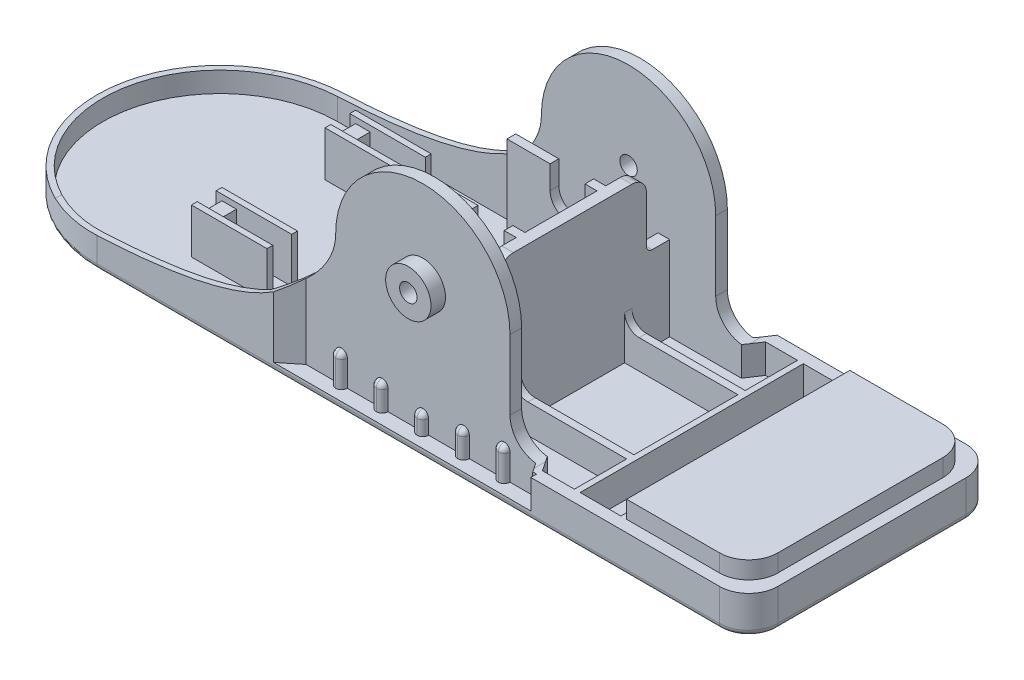
SolidWorks part; units mm, degrees
ref_plane "Front Plane" through (0, 0, 0) normal (0, 0, 1) x (1, 0, 0)
ref_plane "Top Plane" through (0, 0, 0) normal (0, 1, 0) x (1, 0, 0)
ref_plane "Right Plane" through (0, 0, 0) normal (1, 0, 0) x (0, 0, -1)
sketch "Sketch1" plane through (0, 0, 0) normal (0, 1, 0) x (1, 0, 0)
  line L0 (-66.675, 0) -> (-45.475, 0)
  line L1 (-45.475, -21.2) -> (66.675, -21.2)
  line L2 (-66.675, -21.2) -> (-66.675, 0) construction
  line L3 (-45.475, 21.2) -> (66.675, 21.2)
  line L4 (66.675, -21.2) -> (66.675, 21.2)
  line L5 (-66.675, -21.2) -> (66.675, 21.2) construction
  line L6 (-66.675, 21.2) -> (66.675, -21.2) construction
  line L7 (-66.675, 0) -> (-66.675, 21.2) construction
  line L8 (-66.675, 21.2) -> (-45.475, 21.2) construction
  line L9 (-66.675, -21.2) -> (-45.475, -21.2) construction
  arc A0 (-45.475, 21.2) -> (-45.475, -21.2) centre (-45.475, 0) ccw
  arc A1 (-45.475, -21.2) -> (-25.946, -8.2498) centre (-45.475, 0) ccw construction
  arc A2 (-25.946, -8.2498) -> (-25.946, 8.2498) centre (-45.475, 0) ccw construction
  arc A3 (-25.946, 8.2498) -> (-45.475, 21.2) centre (-45.475, 0) ccw construction
  point P0 (0, 0)
  dimension "D1" = 133.35
  dimension "D2" = 42.4
  dimension "D3" = 21.2
extrude "Boss-Extrude1" add sketch "Sketch1" along normal blind 1.5 contours L3 L4 L1 A0
fillet "Fillet1" radius 5 2 edges at (66.675, 0.75, -21.2) (66.675, 0.75, 21.2)
sketch "Sketch3" plane through (0, 1.5, 0) normal (0, 1, 0) x (1, 0, 0)
  line L0 (66.675, -21.2) -> (29.175, -21.2)
  line L1 (-45.475, -21.2) -> (61.675, -21.2) construction
  line L2 (29.175, -21.2) -> (29.175, 21.2)
  line L3 (-45.475, 21.2) -> (61.675, 21.2) construction
  line L4 (29.175, 21.2) -> (66.675, 21.2)
  line L5 (66.675, 21.2) -> (66.675, -21.2)
  line L6 (59.675, -19.2) -> (31.175, -19.2)
  line L8 (31.175, 19.2) -> (59.675, 19.2)
  line L9 (64.675, 14.2) -> (64.675, -14.2)
  line L10 (31.175, 19.2) -> (64.675, 19.2) construction
  line L11 (64.675, 19.2) -> (64.675, -19.2) construction
  line L12 (64.675, -19.2) -> (31.175, -19.2) construction
  line L13 (64.675, -19.2) -> (35.675, -19.2)
  line L14 (31.175, -19.2) -> (29.175, -19.2)
  line L15 (35.675, -19.2) -> (34.675, -19.2)
  line L16 (35.675, -19.2) -> (35.675, 19.2)
  line L17 (35.675, 19.2) -> (34.675, 19.2)
  line L18 (34.675, -19.2) -> (34.675, 19.2)
  line L19 (31.175, 19.2) -> (29.175, 19.2)
  line L20 (64.675, -0.7956) -> (43.675, -0.7956) construction
  line L21 (31.175, -19.2) -> (31.175, 19.2) construction
  line L23 (43.675, 19.2) -> (42.675, 19.2)
  line L24 (43.675, 19.2) -> (43.675, -19.2)
  line L25 (43.675, -19.2) -> (42.675, -19.2)
  line L26 (42.675, 19.2) -> (42.675, -19.2)
  arc A0 (59.675, 19.2) -> (64.675, 14.2) centre (59.675, 14.2) cw
  arc A1 (59.675, -19.2) -> (64.675, -14.2) centre (59.675, -14.2) ccw
  line M21 (66.675, -16.2) -> (66.675, 16.2)
  arc M22 (66.675, 16.2) -> (61.675, 21.2) centre (61.675, 16.2) ccw
  line M23 (61.675, 21.2) -> (-45.475, 21.2)
  line M25 (-45.475, -21.2) -> (61.675, -21.2)
  arc M26 (61.675, -21.2) -> (66.675, -16.2) centre (61.675, -16.2) ccw
  dimension "D3" = 5
  dimension "D1" = 37.5
  dimension "D4" = 29
  dimension "D5" = 1
  dimension "D6" = 0
  dimension "D7" = 21
  dimension "D8" = 1
  dimension "D2" = 2
extrude "Boss-Extrude2" add sketch "Sketch3" along normal blind 5 contours A1 L6 L13 L14 L2 L19 L8 A0 L9 M25 M26 M21 M22 M23 | L26 L25 L24 L23 | L16 L17 L18 L15 region at (45.425, 1.5, 20.634)
extrude "Boss-Extrude3" add sketch "Sketch3<3>" along normal blind 8 separate body contours L6 A1 L9 A0 L8 L24 region at (54.0485, 1.5, 0)
sketch "Sketch3<3>" plane through (0, 1.5, 0) normal (0, 1, 0) x (1, 0, 0) same geometry as "Sketch3"
sketch "Sketch6" plane through (0, 1.5, 0) normal (0, 1, 0) x (1, 0, 0)
  line L0 (29.175, -21.2) -> (27.5167, -18.7)
  line L1 (29.175, -21.2) -> (61.675, -21.2) construction
  line L2 (29.175, -19.2) -> (27.5167, -16.7)
  line L3 (-45.475, -21.2) -> (29.175, -21.2) construction
  line L4 (27.5167, -18.7) -> (-11.9833, -18.7)
  line L5 (27.5167, -16.7) -> (-11.9833, -16.7)
  line L6 (-11.9833, -18.7) -> (-15.1058, -21.2)
  line L7 (-11.9833, -16.7) -> (-16.3548, -20.2)
  line L8 (-45.475, 21.2) -> (29.175, 21.2) construction
  line L9 (-45.475, 21.2) -> (-16.3548, 21.2)
  line L10 (28.5117, -20.2) -> (29.175, -20.2)
  line L11 (-45.475, -20.2) -> (29.175, -20.2)
  line L12 (-45.475, -20.2) -> (-16.3548, -20.2)
  line L13 (-16.3548, -20.2) -> (-13.8568, -20.2) construction
  line L14 (-13.8568, -20.2) -> (28.5117, -20.2) construction
  line L15 (-45.475, -21.2) -> (-16.3548, -21.2)
  line L16 (27.5167, 16.7) -> (-11.9833, 16.7)
  line L17 (-16.3548, 21.2) -> (-15.1058, 21.2)
  line L18 (-16.3548, -21.2) -> (-15.1058, -21.2)
  line L19 (29.175, -19.2) -> (29.175, -21.2)
  line L20 (-45.475, 20.2) -> (-16.3548, 20.2)
  line L21 (-11.9833, 16.7) -> (-16.3548, 20.2)
  line L22 (-11.9833, 18.7) -> (-15.1058, 21.2)
  line L23 (27.5167, 18.7) -> (-11.9833, 18.7)
  line L24 (29.175, 19.2) -> (27.5167, 16.7)
  line L25 (29.175, 21.2) -> (27.5167, 18.7)
  line L26 (29.175, 19.2) -> (29.175, 21.2)
  arc A0 (-45.475, 21.2) -> (-45.475, -21.2) centre (-45.475, 0) ccw
  arc A4 (-45.475, 20.2) -> (-45.475, -20.2) centre (-45.475, 0) ccw
  arc A5 (-45.475, 20.2) -> (-45.475, -20.2) centre (-45.475, 0) ccw
  line M22 (29.175, 19.2) -> (29.175, 21.2)
  line M23 (29.175, 21.2) -> (-45.475, 21.2)
  arc M24 (-45.475, 21.2) -> (-45.475, -21.2) centre (-45.475, 0) ccw
  line M25 (-45.475, -21.2) -> (29.175, -21.2)
  line M26 (29.175, -21.2) -> (29.175, -19.2)
  dimension "D1" = 2.5
  dimension "D2" = 3
  dimension "D3" = 39.5
  dimension "D4" = 2.5
  dimension "D5" = 2
  dimension "D6" = 4
  dimension "D7" = 2.5
  dimension "D9" = 3
  dimension "D10" = 2.5
  dimension "D8" = 1
  dimension "D11" = 1
extrude "Boss-Extrude4" add sketch "Sketch6" along normal blind 37 contours A5 L20 L21 L16 L24 L25 L23 L22 L6 L4 L0 L10 L2 L5 L7 L12 M22 M23 M24 M25 M26 region at (6.9463, 1.5, 17.8201) region at (-15.7303, 1.5, 21.0952)
sketch "Sketch9" plane through (0, 0, 21.2) normal (0, 0, 1) x (1, 0, 0)
  line L0 (-66.675, 38.5) -> (-45.475, 38.5)
  line L1 (8.1, 0) -> (8.1, 23.5)
  line L2 (-45.475, 0) -> (61.675, 0) construction
  line L3 (8.1, 0) -> (-141.45, 0)
  line L4 (-66.675, 0) -> (-66.675, 5)
  line L5 (-66.675, 5) -> (-13.2209, 5) construction
  line L6 (-66.675, 5) -> (-66.675, 38.5)
  line L7 (8.1, 38.5) -> (-66.675, 38.5)
  line L8 (29.175, 6.5) -> (23.1, 23.5)
  line L9 (23.1, 23.5) -> (23.1, 11.5)
  line L10 (28.1, 6.5) -> (29.175, 6.5)
  line L11 (8.1, 38.5) -> (29.175, 38.5)
  line L12 (29.175, 38.5) -> (29.175, 6.5)
  circle A0 centre (8.1, 23.5) radius 15
  arc A1 (23.1, 11.5) -> (28.1, 6.5) centre (28.1, 11.5) ccw
  spline S0 degree 3 poles (-6.9, 23.5) (-6.9, 19.2277) (-18.2844, 4.0271) (-52.7634, 5) (-66.675, 5) knots 0 0 0 0 0.343246 1 1 1 1
  line M10 (-15.1058, 1.5) -> (-15.1058, 38.5)
  line M11 (-15.1058, 38.5) -> (-45.475, 38.5)
  line M12 (-45.475, 38.5) -> (-45.475, 0)
  dimension "D2" = 30
  dimension "D4" = 5
  dimension "D1" = 23.5
  dimension "D3" = 5
extrude "Cut-Extrude1" cut sketch "Sketch9" against normal through all both and the other way through all contours S0 A0 L7 M10 | S0 M10 M11 M12 | L6 L5 S0 L0 M12 | A0 L8 L12 L11 | L9 A1 L10 L8 region at (-56.0848, 21.7705, 21.2) region at (-30.7898, 22.8769, 21.2) region at (-9.692, 28.6572, 21.2) region at (24.7967, 28.49, 21.2) region at (25.2303, 12.6942, 21.2)
sketch "Sketch10" plane through (0, 0, 0) normal (0, -1, 0) x (1, 0, 0)
  line L0 (-66.675, 0) -> (-56.675, 0) construction
  line L1 (-56.675, 0) -> (-45.475, 0) construction
  line L2 (-45.475, -11.2) -> (-45.475, 11.2)
  arc A0 (-45.475, 21.2) -> (-45.475, -21.2) centre (-45.475, 0) ccw construction
  arc A1 (-45.475, 11.2) -> (-45.475, -11.2) centre (-45.475, 0) ccw
  arc A2 (-45.475, -11.2) -> (-45.475, 11.2) centre (-45.475, 0) ccw construction
  point P11 (-45.475, 0)
  dimension "D1" = 22.4
extrude "Cut-Extrude2" cut sketch "Sketch10" against normal blind 0.5 contours L2 A1
sketch "Sketch11" plane through (0, 1.5, 0) normal (0, 1, 0) x (1, 0, 0)
  line L0 (29.175, 19.2) -> (29.175, 10.2) construction
  line L1 (34.675, 10.2) -> (15.175, 10.2)
  line L2 (34.675, -19.2) -> (34.675, 19.2) construction
  line L3 (29.175, -19.2) -> (29.175, -10.2) construction
  line L4 (34.675, -10.2) -> (15.175, -10.2)
  line L5 (15.175, -16.7) -> (15.175, 16.7)
  line L6 (27.5167, -16.7) -> (-11.9833, -16.7) construction
  line L7 (27.5167, 16.7) -> (-11.9833, 16.7) construction
  line L8 (23.1, -16.7) -> (-6.9, -16.7) construction
  line L9 (15.175, 16.7) -> (13.175, 16.7)
  line L10 (15.175, 16.7) -> (15.175, -16.7)
  line L11 (15.175, -16.7) -> (13.175, -16.7)
  line L12 (13.175, 16.7) -> (13.175, -16.7)
  line L13 (15.175, 10.2) -> (15.175, 8.95)
  line L14 (15.175, 8.95) -> (34.675, 8.95)
  line L15 (15.175, -10.2) -> (15.175, -8.95)
  line L16 (15.175, -8.95) -> (34.675, -8.95)
  line L17 (15.175, -16.7) -> (15.175, -12.7)
  line L18 (15.175, -12.7) -> (13.175, -12.7)
  line L19 (13.175, 16.7) -> (13.175, 7.7)
  line L20 (13.175, 7.7) -> (15.175, 7.7)
  line L21 (13.175, -16.7) -> (13.175, -7.7)
  line L22 (13.175, 16.7) -> (13.175, 7.7)
  line L24 (13.175, 7.7) -> (-2.325, 7.7)
  line L25 (13.175, 7.7) -> (13.175, 6.2)
  line L26 (13.175, 6.2) -> (-2.325, 6.2)
  line L27 (-2.325, 7.7) -> (-2.325, 6.2)
  line L28 (13.175, -7.7) -> (-2.325, -7.7)
  line L29 (13.175, -7.7) -> (13.175, -6.2)
  line L30 (13.175, -6.2) -> (-2.325, -6.2)
  line L31 (-2.325, -7.7) -> (-2.325, -6.2)
  line L32 (13.175, 16.7) -> (15.175, 16.7)
  line L33 (13.175, 16.7) -> (13.175, 12.7)
  line L34 (13.175, 12.7) -> (15.175, 12.7)
  line L35 (15.175, 16.7) -> (15.175, 12.7)
  line M9 (27.5167, 16.7) -> (-11.9833, 16.7)
  line M15 (-11.9833, -16.7) -> (27.5167, -16.7)
  line M18 (34.675, -19.2) -> (34.675, 19.2)
  dimension "D1" = 9
  dimension "D2" = 19.5
  dimension "D3" = 9
  dimension "D4" = 2
  dimension "D5" = 1.25
  dimension "D6" = 1.25
  dimension "D7" = 4
  dimension "D8" = 9
  dimension "D9" = 9
  dimension "D10" = 9
  dimension "D11" = 1.5
  dimension "D12" = 15.5
  dimension "D13" = 1.5
  dimension "D14" = 15.5
  dimension "D15" = 4
extrude "Boss-Extrude5" add sketch "Sketch11" along normal up to surface (5 mm away) contours L16 L5 L4 M18 | L5 L18 L12 M15 | L20 L12 L22 L18 L10 L5 | L31 L28 L12 L30 | L10 L14 L1 M18 | L12 L20 L10 M9 | L24 L27 L26 L12 | L34 L22 L20 L5 L10 region at (24.925, 1.5, -9.575) region at (14.175, 1.5, -10.2) region at (14.175, 1.5, -14.7) region at (24.925, 1.5, 9.575) region at (14.175, 1.5, 2.5) region at (5.425, 1.5, -6.95) region at (14.175, 1.5, 14.7) region at (5.425, 1.5, 6.95) up to face at (38.4317, 6.5, 2.4)
extrude "Boss-Extrude6" add sketch "Sketch11<6>" along normal blind 26 contours L34 L22 L20 L5 L10 | L20 L12 L18 L10 L5 | L28 L31 L30 L29 | L24 L27 L26 L25 region at (14.175, 1.5, 2.5) region at (14.175, 1.5, -10.2)
sketch "Sketch11<6>" plane through (0, 1.5, 0) normal (0, 1, 0) x (1, 0, 0) same geometry as "Sketch11"
extrude "Boss-Extrude7" add sketch "Sketch11<7>" along normal blind 14.5 contours L5 L18 L12 M15 | L12 L34 L10 M9 region at (14.175, 1.5, 14.7) region at (14.175, 1.5, -14.7)
sketch "Sketch11<7>" plane through (0, 1.5, 0) normal (0, 1, 0) x (1, 0, 0) same geometry as "Sketch11"
fillet "Fillet2" radius 2.5 2 edges at (15.175, 6.5, 9.575) (15.175, 6.5, -9.575)
fillet "Fillet3" radius 1 2 edges at (14.175, 16, -12.7) (14.175, 16, 12.7)
fillet "Fillet4" radius 2.5 2 edges at (14.175, 27.5, -12.7) (14.175, 27.5, 12.7)
sketch "Sketch13" plane through (0, 0, -18.7) normal (0, 0, -1) x (-1, 0, 0)
  line L0 (-8.1, 38.5) -> (-8.1, 23.5) construction
  arc A0 (6.9, 23.5) -> (-23.1, 23.5) centre (-8.1, 23.5) ccw construction
  circle A1 centre (-8.1, 23.5) radius 1.5
  circle A2 centre (-8.1, 23.5) radius 3.9
  dimension "D1" = 3
  dimension "D2" = 7.8
extrude "Cut-Extrude3" cut sketch "Sketch13" against normal through all both and the other way through all contours A1
extrude "Boss-Extrude9" add sketch "Sketch13<3>" along normal blind 2.5
sketch "Sketch13<3>" plane through (0, 0, -18.7) normal (0, 0, -1) x (-1, 0, 0) same geometry as "Sketch13"
sketch "Sketch15" plane through (0, 0, 18.7) normal (0, 0, 1) x (1, 0, 0)
  line L0 (8.1, 38.5) -> (8.1, 23.5)
  arc A0 (23.1, 23.5) -> (-6.9, 23.5) centre (8.1, 23.5) ccw construction
  circle A1 centre (8.1, 23.5) radius 3.9
  circle M2 centre (8.1, 23.5) radius 1.5
  dimension "D1" = 7.8
extrude "Boss-Extrude10" add sketch "Sketch15" along normal blind 2.5 contours A1 M2 region at (10.7797, 26.1797, 18.7)
sketch "Sketch16" plane through (0, 0, 7.7) normal (0, 0, 1) x (1, 0, 0)
  line L0 (13.175, 27.5) -> (8.1, 23.5) construction
  line L1 (8.1, 23.5) -> (8.1, 27.5) construction
  line L2 (13.175, 27.5) -> (-2.325, 27.5) construction
  line L3 (5.1, 23.5) -> (5.1, 27.5)
  line L4 (11.1, 23.5) -> (11.1, 27.5)
  circle A0 centre (8.1, 23.5) radius 3
  circle M2 centre (8.1, 23.5) radius 1.5
  line M4 (13.175, 27.5) -> (-2.325, 27.5)
  dimension "D1" = 6
extrude "Cut-Extrude4" cut sketch "Sketch16" against normal up to surface (15.4 mm away) contours A0 L4 L3 M4 | A0 M2 region at (8.1, 26.5417, 7.7) region at (8.1, 26.4151, 7.7) up to face at (9.6, 23.5, -7.7)
sketch "Sketch18" plane through (0, 1.5, 0) normal (0, 1, 0) x (1, 0, 0)
  line L0 (-31.3725, 20.2) -> (-31.3725, 15.7)
  line L1 (-45.475, 20.2) -> (-16.3548, 20.2) construction
  line L2 (-37.8725, 15.7) -> (-24.8725, 15.7)
  line L3 (-37.8725, 15.7) -> (-37.8725, 14.7)
  line L4 (-37.8725, 14.7) -> (-24.8725, 14.7)
  line L5 (-24.8725, 14.7) -> (-24.8725, 15.7)
  line L6 (-36.8725, 14.7) -> (-34.3725, 14.7)
  line L7 (-37.8725, 14.7) -> (-36.8725, 14.7)
  line L8 (-37.8725, 14.7) -> (-37.8725, 11.45) construction
  line L9 (-37.8725, 11.45) -> (-36.8725, 11.45)
  line L10 (-36.8725, 14.7) -> (-36.8725, 11.45)
  line L11 (-34.3725, 14.7) -> (-34.3725, 11.45)
  line L12 (-34.3725, 11.45) -> (-24.8725, 11.45)
  line L13 (-24.8725, 11.45) -> (-24.8725, 10.45)
  line L14 (-24.8725, 10.45) -> (-37.8725, 10.45)
  line L15 (-37.8725, 10.45) -> (-37.8725, 11.45)
  line L16 (-36.8725, 13.075) -> (-60.8725, 13.075)
  line L17 (-36.8725, 11.45) -> (-34.3725, 11.45)
  line L18 (-31.3725, -12.55) -> (-31.3725, -20.2)
  line L19 (-37.8725, -7.3) -> (-24.8725, -7.3)
  line L20 (-37.8725, -7.3) -> (-37.8725, -8.3)
  line L21 (-37.8725, -8.3) -> (-24.8725, -8.3)
  line L22 (-24.8725, -8.3) -> (-24.8725, -7.3)
  line L23 (-36.8725, -8.3) -> (-34.3725, -8.3)
  line L24 (-37.8725, -8.3) -> (-36.8725, -8.3)
  line L25 (-37.8725, -8.3) -> (-37.8725, -11.55) construction
  line L26 (-37.8725, -11.55) -> (-36.8725, -11.55)
  line L27 (-36.8725, -8.3) -> (-36.8725, -11.55)
  line L28 (-34.3725, -8.3) -> (-34.3725, -11.55)
  line L29 (-34.3725, -11.55) -> (-24.8725, -11.55)
  line L30 (-24.8725, -11.55) -> (-24.8725, -12.55)
  line L31 (-24.8725, -12.55) -> (-37.8725, -12.55)
  line L32 (-37.8725, -12.55) -> (-37.8725, -11.55)
  line L33 (-45.475, -20.2) -> (-16.3548, -20.2) construction
  line L34 (-36.8725, -11.55) -> (-34.3725, -11.55)
  arc A0 (-45.475, 20.2) -> (-45.475, -20.2) centre (-45.475, 0) ccw construction
  point P6 (-31.3725, 15.7)
  point P26 (-31.3725, -7.3)
  dimension "D1" = 4.5
  dimension "D2" = 1
  dimension "D3" = 13
  dimension "D4" = 3.25
  dimension "D5" = 1
  dimension "D6" = 2.5
  dimension "D7" = 1
  dimension "D8" = 24
  dimension "D9" = 7.65
  dimension "D10" = 1
  dimension "D11" = 13
  dimension "D12" = 3.25
  dimension "D13" = 1
  dimension "D14" = 2.5
  dimension "D15" = 1
extrude "Boss-Extrude11" add sketch "Sketch18" along normal blind 7.75 contours L34 L26 L32 L31 L30 L29 | L21 L22 L19 L20 | L17 L9 L15 L14 L13 L12 | L4 L5 L2 L3 region at (-31.3725, 1.5, -15.2) region at (-31.3725, 1.5, -10.95) region at (-31.3725, 1.5, 7.8) region at (-31.3725, 1.5, 12.05)
extrude "Boss-Extrude12" add sketch "Sketch18<6>" along normal blind 6.75 contours L10 L17 L11 L4 | L27 L34 L28 L21 region at (-35.6225, 1.5, -13.075) region at (-35.6225, 1.5, 9.925)
sketch "Sketch18<6>" plane through (0, 1.5, 0) normal (0, 1, 0) x (1, 0, 0) same geometry as "Sketch18"
sketch "Sketch19" plane through (0, 0, 18.7) normal (0, 0, 1) x (1, 0, 0)
  line L0 (8.1, 23.5) -> (8.1, 1.5)
  line L1 (-15.1058, 1.5) -> (29.175, 1.5) construction
  line L2 (8.1, 1.5) -> (8.1, 5)
  line L3 (7.1, 5) -> (9.1, 5)
  line L4 (27.5167, 1.5) -> (-11.9833, 1.5) construction
  line L5 (9.1, 5) -> (7.1, 5)
  line L6 (9.1, 5) -> (9.1, 1.5)
  line L7 (9.1, 1.5) -> (7.1, 1.5)
  line L8 (7.1, 5) -> (7.1, 1.5)
  line L9 (9.1, 1.5) -> (14.1, 1.5)
  line L10 (16.1, 1.5) -> (21.1, 1.5)
  line L11 (14.1, 1.5) -> (16.1, 1.5)
  line L12 (14.1, 1.5) -> (14.1, 6)
  line L13 (14.1, 6) -> (16.1, 6)
  line L14 (16.1, 1.5) -> (16.1, 6)
  line L16 (21.1, 1.5) -> (23.1, 1.5)
  line L17 (21.1, 1.5) -> (21.1, 7)
  line L18 (21.1, 7) -> (23.1, 7)
  line L19 (23.1, 1.5) -> (23.1, 7)
  line L21 (2.1, 1.5) -> (2.1, 6)
  line L28 (2.1, 1.5) -> (0.1, 1.5)
  line L29 (-6.9, 1.5) -> (-6.9, 7)
  line L30 (-4.9, 7) -> (-6.9, 7)
  line L31 (-4.9, 1.5) -> (-4.9, 7)
  line L32 (-4.9, 1.5) -> (-6.9, 1.5)
  line L33 (0.1, 1.5) -> (0.1, 6)
  line L34 (2.1, 6) -> (0.1, 6)
  line L35 (0.1, 1.5) -> (-4.9, 1.5)
  point P9 (8.1, 5)
  line M18 (-11.9833, 1.5) -> (27.5167, 1.5)
  dimension "D1" = 3.5
  dimension "D2" = 2
  dimension "D3" = 5
  dimension "D4" = 2
  dimension "D5" = 4.5
  dimension "D6" = 5
  dimension "D7" = 2
  dimension "D8" = 5.5
  dimension "D9" = 5
  dimension "D10" = 2
  dimension "D11" = 2
  dimension "D12" = 5.5
  dimension "D13" = 4.5
  dimension "D14" = 5
sketch "Sketch20" plane through (0, 0, -18.7) normal (0, 0, -1) x (-1, 0, 0)
  line L0 (-8.1, 23.5) -> (-8.1, 1.5)
  line L1 (-8.1, 1.5) -> (-8.1, 5)
  line L2 (-9.1, 5) -> (-7.1, 5)
  line L3 (-7.1, 5) -> (-9.1, 5)
  line L4 (-7.1, 5) -> (-7.1, 1.5)
  line L5 (-7.1, 1.5) -> (-9.1, 1.5)
  line L6 (-9.1, 5) -> (-9.1, 1.5)
  line L7 (-7.1, 1.5) -> (-2.1, 1.5)
  line L8 (-0.1, 1.5) -> (4.9, 1.5)
  line L9 (-2.1, 1.5) -> (-0.1, 1.5)
  line L10 (-2.1, 1.5) -> (-2.1, 6)
  line L11 (-2.1, 6) -> (-0.1, 6)
  line L12 (-0.1, 1.5) -> (-0.1, 6)
  line L13 (4.9, 1.5) -> (6.9, 1.5)
  line L14 (4.9, 1.5) -> (4.9, 7)
  line L15 (4.9, 7) -> (6.9, 7)
  line L16 (6.9, 1.5) -> (6.9, 7)
  line L17 (-14.1, 1.5) -> (-14.1, 6)
  line L18 (-14.1, 1.5) -> (-16.1, 1.5)
  line L19 (-23.1, 1.5) -> (-23.1, 7)
  line L20 (-21.1, 7) -> (-23.1, 7)
  line L21 (-21.1, 1.5) -> (-21.1, 7)
  line L22 (-21.1, 1.5) -> (-23.1, 1.5)
  line L23 (-16.1, 1.5) -> (-16.1, 6)
  line L24 (-14.1, 6) -> (-16.1, 6)
  line L25 (-16.1, 1.5) -> (-21.1, 1.5)
  line L26 (-27.5167, 1.5) -> (11.9833, 1.5) construction
  point P6 (-8.1, 5)
  line M20 (-27.5167, 1.5) -> (11.9833, 1.5)
  dimension "D1" = 3.5
  dimension "D2" = 2
  dimension "D3" = 5
  dimension "D4" = 2
  dimension "D5" = 4.5
  dimension "D6" = 5
  dimension "D7" = 2
  dimension "D8" = 5.5
  dimension "D9" = 5
  dimension "D10" = 2
  dimension "D11" = 2
  dimension "D12" = 5.5
  dimension "D13" = 4.5
  dimension "D14" = 5
extrude "Boss-Extrude13" add sketch "Sketch19" along normal blind 1 contours L31 L30 L29 M18 | L21 L34 L33 M18 | L6 L3 L0 M18 | L3 L8 L0 M18 | L14 L13 L12 M18 | L19 L18 L17 M18 region at (8.6, 3.25, 18.7) region at (7.6, 3.25, 18.7) region at (22.1, 4.25, 18.7) region at (15.1, 3.75, 18.7) region at (-5.9, 4.25, 18.7) region at (1.1, 3.75, 18.7)
fillet "Fillet5" radius 1 25 edges at (23.1, 7, 19.2) (21.1, 7, 19.2) (22.1, 7, 19.7) (16.1, 6, 19.2) (15.1, 6, 19.7) (14.1, 6, 19.2) (9.1, 5, 19.2) (7.1, 5, 19.2) (8.1, 5, 19.7) (-5.9, 7, 19.7) (1.1, 6, 19.7) (2.1, 6, 19.2) (0.1, 6, 19.2) (-4.9, 7, 19.2) (-6.9, 7, 19.2) (21.1, 4.25, 19.7) (23.1, 4.25, 19.7) (16.1, 3.75, 19.7) (14.1, 3.75, 19.7) (7.1, 3.25, 19.7) (9.1, 3.25, 19.7) (0.1, 3.75, 19.7) (2.1, 3.75, 19.7) (-6.9, 4.25, 19.7) (-4.9, 4.25, 19.7)
extrude "Boss-Extrude14" add sketch "Sketch20" along normal blind 1 contours L21 L20 L19 M20 | L17 L24 L23 M20 | L4 L2 L0 M20 | L2 L6 L0 M20 | L12 L11 L10 M20 | L16 L15 L14 M20 region at (7.6, 3.25, -18.7) region at (8.6, 3.25, -18.7) region at (-5.9, 4.25, -18.7) region at (1.1, 3.75, -18.7) region at (22.1, 4.25, -18.7) region at (15.1, 3.75, -18.7)
fillet "Fillet6" radius 1 25 edges at (-4.9, 7, -19.2) (-5.9, 7, -19.7) (-6.9, 7, -19.2) (2.1, 6, -19.2) (1.1, 6, -19.7) (0.1, 6, -19.2) (9.1, 5, -19.2) (8.1, 5, -19.7) (7.1, 5, -19.2) (16.1, 6, -19.2) (15.1, 6, -19.7) (14.1, 6, -19.2) (23.1, 7, -19.2) (22.1, 7, -19.7) (21.1, 7, -19.2) (-4.9, 4.25, -19.7) (-6.9, 4.25, -19.7) (2.1, 3.75, -19.7) (0.1, 3.75, -19.7) (9.1, 3.25, -19.7) (7.1, 3.25, -19.7) (16.1, 3.75, -19.7) (14.1, 3.75, -19.7) (23.1, 4.25, -19.7) (21.1, 4.25, -19.7)
fillet "Fillet7" radius 1 8 edges at (-66.675, 0, 0) (8.1, 0, 21.2) (65.2105, 0, 19.7355) (66.675, 0, 0) (65.2105, 0, -19.7355) (8.1, 0, -21.2) (-45.475, 0, 0) (-56.675, 0, 0)
